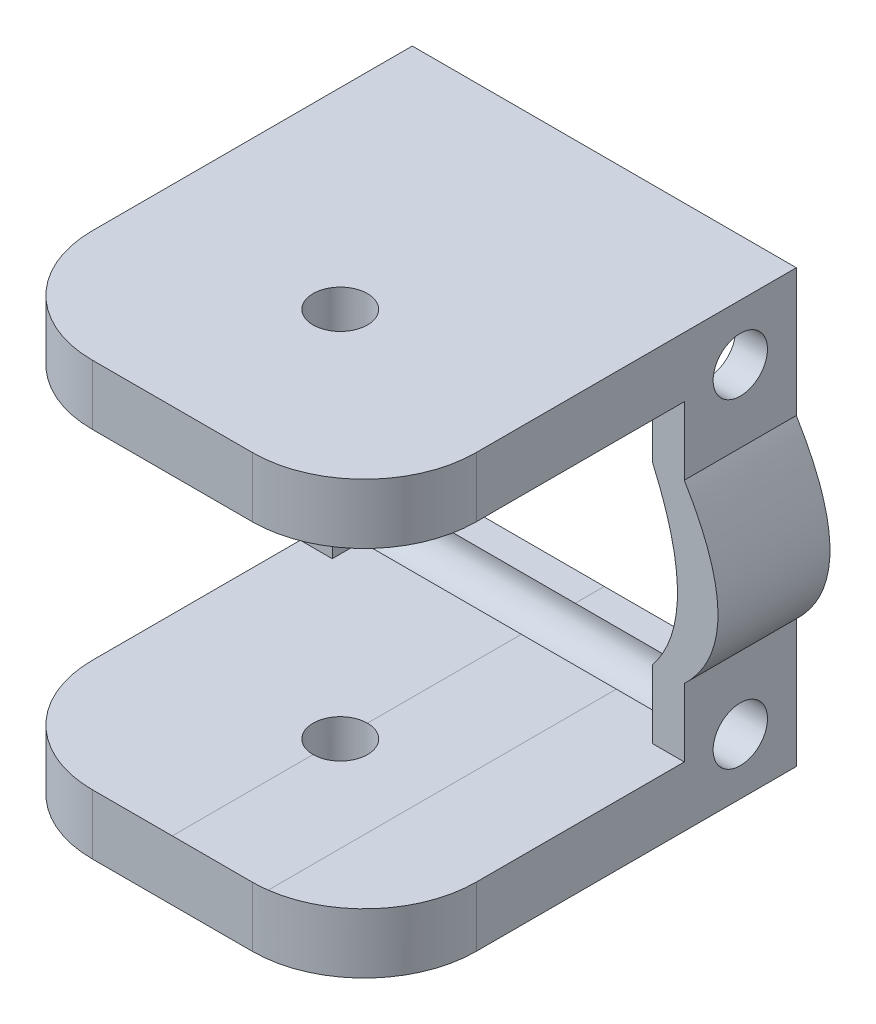
SolidWorks part; units mm, degrees
material "PLA"
ref_plane "Front Plane" through (0, 0, 0) normal (0, 0, 1) x (1, 0, 0)
ref_plane "Top Plane" through (0, 0, 0) normal (0, 1, 0) x (1, 0, 0)
ref_plane "Right Plane" through (0, 0, 0) normal (1, 0, 0) x (0, 0, -1)
sketch "Sketch1" plane through (0, 0, 0) normal (0, 0, 1) x (1, 0, 0)
  line L0 (-12, 13.5) -> (-12, 9.75)
  line L1 (-12, 9.75) -> (12, 9.75)
  line L2 (12, 9.75) -> (12, 13.5)
  line L3 (12, 13.5) -> (-12, 13.5)
  line L4 (-12, -9.75) -> (-12, -13.5)
  line L5 (-12, -13.5) -> (12, -13.5)
  line L6 (12, -13.5) -> (12, -9.75)
  line L7 (12, -9.75) -> (-12, -9.75)
  line L8 (0, 10.0333) -> (0, -15.702) construction
  line L9 (-12, 9.75) -> (-12, -9.75) construction
  line L10 (12, 9.75) -> (12, -9.75) construction
  line L11 (12, 9.75) -> (12, 5.5)
  line L12 (12, -9.75) -> (12, -5.5)
  line L13 (10, 9.75) -> (10, 5.5)
  line L14 (10, -9.75) -> (10, -5.5)
  line L17 (-10, -9.75) -> (-10, -5.5)
  line L18 (0, 0) -> (14.9553, 0) construction
  line L19 (-12, -9.75) -> (-12, -5.5)
  line L20 (-12, 9.75) -> (-12, 5.5)
  line L21 (-10, 9.75) -> (-10, 5.5)
  spline S0 degree 2 poles (12, 5.5) (16.2082, -1.4527) (12, -5.5) knots 0 0 0 0.703674 0.703674 0.703674
  spline S1 degree 2 poles (5.9341, -9.75) (5.4786, -9.7593) (0, -9.75) knots 0.968743 0.968743 0.968743 1 1 1
  spline S2 degree 2 poles (10, 5.5) (13.145, -1.5935) (10, -5.5) knots 0 0 0 0.703674 0.703674 0.703674
  spline S3 degree 2 poles (-12, 5.5) (-16.2082, -1.4527) (-12, -5.5) knots 0 0 0 0.703674 0.703674 0.703674
  spline S4 degree 2 poles (-10, 5.5) (-13.145, -1.5935) (-10, -5.5) knots 0 0 0 0.703674 0.703674 0.703674
  point P9 (0, -9.75)
  point P21 (12, 7.625)
  dimension "D6" = 8
  dimension "D5" = 8
  dimension "D1" = 3.75
  dimension "D2" = 3.75
  dimension "D3" = 24
  dimension "D4" = 27
  dimension "D7" = 2
extrude "Boss-Extrude1" add sketch "Sketch1" along normal blind 7 contours L2 L3 L0 L1 | S4 L21 L1 L20 S3 L19 L7 L17 | L13 S2 L14 L7 L12 S0 L11 L1 | L7 S1 L4 L5 L6 region at (0, 11.625, 0) region at (-11.7621, -0.0188, 0) region at (11.7621, -0.0188, 0) region at (-0.0007, -11.6254, 0)
extrude "Boss-Extrude2" add sketch "Sketch1<3>" along normal blind 20 from surface contours L2 L3 L0 L1 | L6 L7 L4 L5 region at (0, 11.625, 0) region at (-0.0007, -11.6254, 0) starting at face at (0.8901, -0.85, 7)
sketch "Sketch1<3>" plane through (0, 0, 0) normal (0, 0, 1) x (1, 0, 0) same geometry as "Sketch1"
fillet "Fillet1" radius 7 4 edges at (12, -11.625, 27) (-12, -11.625, 27) (12, 11.625, 27) (-12, 11.625, 27)
sketch "Sketch2" plane through (-12, 0, 0) normal (-1, 0, 0) x (0, 0, 1)
  line L0 (20, -13.5) -> (0, -13.5) construction
  line L3 (3.5, 10) -> (3.5, -10) construction
  line L4 (7, -9.75) -> (7, -5.5) construction
  line L5 (0, -13.5) -> (0, -5.5) construction
  point P0 (3.5, 10)
  point P1 (3.5, -10)
  dimension "D1" = 20
  dimension "D2" = 3.5
hole_wizard "M3 Clearance Hole1" positions "Sketch3" profile "Sketch4" hole size "M3" standard "ISO" end condition through all
sketch "Sketch3" plane through (-12, 0, 0) normal (-1, 0, 0) x (0, 0, 1)
  point P0 (3.5, 10)
  point P3 (3.5, -10)
sketch "Sketch4" plane through (-12, 10, 3.5) normal (0, 1, 0) x (0, 0, 1)
  line L0 (0, 0) -> (0, 26.1041)
  line L1 (0, 26.1041) -> (1.7, 26.1041)
  line L2 (1.7, 26.1041) -> (1.7, 0)
  line L5 (1.7, 0) -> (0, 0)
  line L11 (0, -6.35) -> (0, 107.95) construction
  dimension "Thru Hole Dia." = 3.4
  dimension "Thru Hole Depth" = 26.1041
sketch "Sketch5" plane through (0, 13.5, 0) normal (0, 1, 0) x (1, 0, 0)
  line L0 (12, 0) -> (-12, 0) construction
  point P0 (0, -16.5)
  dimension "D1" = 16.5
hole_wizard "M3 Clearance Hole2" positions "Sketch6" profile "Sketch7" hole size "M3" standard "ISO" end condition through all
sketch "Sketch6" plane through (0, 13.5, 0) normal (0, 1, 0) x (1, 0, 0)
  point P0 (0, -16.5)
sketch "Sketch7" plane through (0, 13.5, 16.5) normal (1, 0, 0) x (0, 0, 1)
  line L0 (0, 0) -> (0, 27)
  line L1 (0, 27) -> (1.7, 27)
  line L2 (1.7, 27) -> (1.7, 0)
  line L5 (1.7, 0) -> (0, 0)
  line L11 (0, -6.35) -> (0, 107.95) construction
  dimension "Thru Hole Dia." = 3.4
  dimension "Thru Hole Depth" = 27
